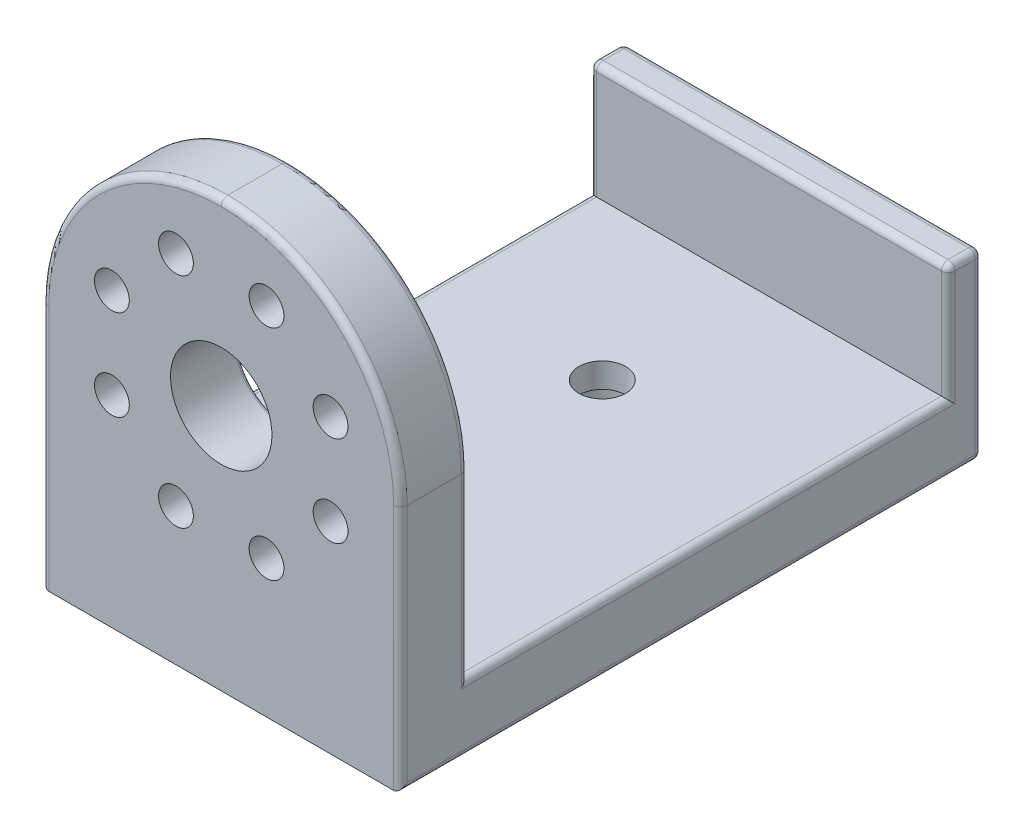
SolidWorks part; units mm, degrees
ref_plane "Front Plane" through (0, 0, 0) normal (0, 0, 1) x (1, 0, 0)
ref_plane "Top Plane" through (0, 0, 0) normal (0, 1, 0) x (1, 0, 0)
ref_plane "Right Plane" through (0, 0, 0) normal (1, 0, 0) x (0, 0, -1)
sketch "Sketch2" plane through (0, 0, 0) normal (1, 0, 0) x (0, 0, -1)
  line L0 (55, 0) -> (-55, 0) construction
  line L1 (-34.9272, -24.891) -> (-24.9272, -24.891)
  line L2 (-34.9272, -24.891) -> (-34.9272, 38.109)
  line L3 (-34.9272, 38.109) -> (-24.9272, 38.109)
  line L4 (-24.9272, -14.891) -> (-24.9272, 38.109)
  line L6 (46.0728, -24.891) -> (51.0728, -24.891)
  line L7 (46.0728, -14.891) -> (46.0728, 2.109)
  line L8 (-24.9272, -24.891) -> (46.0728, -24.891)
  line L10 (-24.9272, -14.891) -> (46.0728, -14.891)
  line L12 (46.0728, 2.109) -> (51.0728, 2.109)
  line L13 (51.0728, -24.891) -> (51.0728, 2.109)
  point P0 (-30.7902, 0)
  dimension "D1" = 63
  dimension "D2" = 10
  dimension "D3" = 10
  dimension "D4" = 71
  dimension "D5" = 27
  dimension "D6" = 5
extrude "Boss-Extrude1" add sketch "Sketch2" along normal mid plane 53
sketch "Sketch3" plane through (0, 0, 24.9272) normal (0, 0, -1) x (-1, 0, 0)
  line L0 (-26.5, 38.109) -> (26.5, 38.109) construction
  line L1 (0, 55) -> (0, -55) construction
  circle A0 centre (0, 11.609) radius 17.5 construction
  circle A1 centre (-6.697, 27.7769) radius 2.575
  circle A16 centre (0, 11.609) radius 7.5
  circle A17 centre (6.697, 27.7769) radius 2.575
  circle A18 centre (16.1679, 18.306) radius 2.575
  circle A19 centre (16.1679, 4.9121) radius 2.575
  circle A20 centre (6.697, -4.5589) radius 2.575
  circle A21 centre (-6.697, -4.5589) radius 2.575
  circle A22 centre (-16.1679, 4.9121) radius 2.575
  circle A23 centre (-16.1679, 18.306) radius 2.575
  point P18 (0, 11.609)
  point P22 (0, 11.609)
  point P23 (12.8062, 6.3045)
  point P25 (0, 0)
  point P26 (0, 0)
  dimension "D1" = 35
  dimension "D2" = 26.5
  dimension "D3" = 5.15
  dimension "D5" = 15
  dimension "D6" = 10.3321
  dimension "D7" = 10.3321
  dimension "D4" = 8
sketch "Sketch4" plane through (0, 0, 24.9272) normal (0, 0, -1) x (-1, 0, 0)
  line L0 (0, 55) -> (0, -55) construction
  line L1 (-26.5, 38.109) -> (26.5, 38.109) construction
  circle A1 centre (0, 11.609) radius 17.5 construction
  circle A11 centre (6.697, -4.5589) radius 4.35
  circle A13 centre (16.1679, 18.306) radius 4.35
  circle A15 centre (6.697, 27.7769) radius 4.35
  circle A16 centre (0, 11.609) radius 7.5
  circle A17 centre (0, 11.609) radius 7.5
  circle A19 centre (-6.697, 27.7769) radius 4.35
  circle A21 centre (-16.1679, 18.306) radius 4.35
  circle A23 centre (-16.1679, 4.9121) radius 4.35
  circle A25 centre (-6.697, -4.5589) radius 4.35
  circle A27 centre (16.1679, 4.9121) radius 4.35
  point P25 (0, 11.609)
  dimension "D1" = 8.7
  dimension "D2" = 35
  dimension "D3" = 26.5
  dimension "D6" = 0
extrude "Cut-Extrude1" cut sketch "Sketch3" against normal through all
extrude "Cut-Extrude2" cut sketch "Sketch4" against normal blind 5
fillet "Fillet1" radius 26.5 2 edges at (-26.5, 38.109, 29.9272) (26.5, 38.109, 29.9272)
sketch "Sketch7" plane through (-26.5, 0, 0) normal (-1, 0, 0) x (0, 0, 1)
  line L0 (10.9272, -14.891) -> (24.9272, -0.891)
  line L1 (-46.0728, -14.891) -> (24.9272, -14.891) construction
  line L2 (24.9272, -14.891) -> (24.9272, 11.609) construction
  line L3 (24.9272, -0.891) -> (24.9272, -14.891)
  line L4 (24.9272, -14.891) -> (10.9272, -14.891)
  dimension "D1" = 14
  dimension "D2" = 14
sketch "Sketch8" plane through (0, 0, 0) normal (0, 1, 0) x (1, 0, 0)
  line L1 (11, 70.0728) -> (35, 70.0728)
  line L2 (11, 70.0728) -> (11, -23.9272)
  line L3 (11, -23.9272) -> (35, -23.9272)
  line L4 (35, 70.0728) -> (35, -23.9272)
  line L5 (11, 70.0728) -> (35, -23.9272) construction
  line L6 (11, -23.9272) -> (35, 70.0728) construction
  line L7 (26.5, -24.9272) -> (-26.5, -24.9272) construction
  line L8 (46.8168, 23.0728) -> (-74.2317, 23.0728) construction
  line L9 (26.5, -24.9272) -> (0, -24.9272) construction
  line L10 (26.5, 46.0728) -> (26.5, -24.9272) construction
  line L11 (-29.5, 45.0728) -> (11, 45.0728)
  line L12 (-29.5, 45.0728) -> (-29.5, 1.0728)
  line L13 (-29.5, 1.0728) -> (11, 1.0728)
  line L14 (11, 45.0728) -> (11, 1.0728)
  line L15 (-29.5, 45.0728) -> (11, 1.0728) construction
  line L16 (-29.5, 1.0728) -> (11, 45.0728) construction
  circle A0 centre (-1.65, 23.0728) radius 3.4529
  point P0 (23, 23.0728)
  point P15 (-9.25, 23.0728)
  point P20 (14.85, 23.0728)
  point P21 (14.85, 23.0728)
  dimension "D5" = 6.9057
  dimension "D6" = 48
  dimension "D7" = 12.65
  dimension "D1" = 94
  dimension "D2" = 24
  dimension "D3" = 8.5
  dimension "D4" = 1
  dimension "D8" = 44
  dimension "D9" = 40.5
  dimension "D10" = 0
sketch "Sketch9" plane through (0, -14.891, 0) normal (0, 1, 0) x (1, 0, 0)
  circle A2 centre (-1.65, 23.0728) radius 3.4529
  circle A3 centre (-1.65, 23.0728) radius 3.4529
  dimension "D1" = 0
extrude "Cut-Extrude8" cut sketch "Sketch9" against normal blind 30
sketch "Sketch10" plane through (0, -24.891, 0) normal (0, -1, 0) x (1, 0, 0)
  circle A1 centre (-1.65, -23.0728) radius 4.825
  dimension "D1" = 9.65
extrude "Cut-Extrude9" cut sketch "Sketch10" against normal blind 6.35
fillet "Fillet2" radius 1 21 edges at (-26.5, -1.641, 24.9272) (-18.7383, 30.3473, 24.9272) (26.5, -1.641, 24.9272) (26.5, -6.641, 34.9272) (-26.5, -6.641, 34.9272) (-18.7383, 30.3473, 34.9272) (-26.5, -14.891, -10.5728) (26.5, -14.891, -10.5728) (-26.5, -24.891, -8.0728) (26.5, -24.891, -8.0728) (18.7383, 30.3473, 24.9272) (18.7383, 30.3473, 34.9272) (-26.5, 2.109, -48.5728) (-26.5, -11.391, -51.0728) (-26.5, -6.391, -46.0728) (0, 2.109, -51.0728) (26.5, 2.109, -48.5728) (0, 2.109, -46.0728) (26.5, -11.391, -51.0728) (26.5, -6.391, -46.0728) (0, -24.891, -51.0728)
fillet "Fillet3" radius 0.5 10 edges at (0, 19.109, 24.9272) (-6.697, -0.2089, 24.9272) (-16.1679, 9.2621, 24.9272) (6.697, -0.2089, 24.9272) (16.1679, 9.2621, 24.9272) (16.1679, 22.656, 24.9272) (-16.1679, 22.656, 24.9272) (-6.697, 32.1269, 24.9272) (6.697, 32.1269, 24.9272) (-1.65, -24.891, -27.8978)
